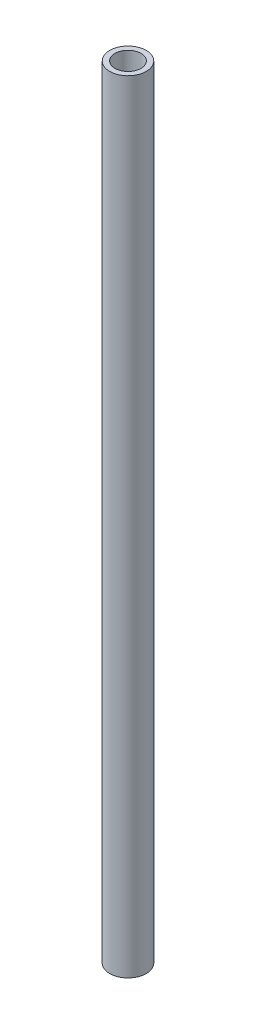
SolidWorks part; units mm, degrees
ref_plane "Płaszczyzna przednia" through (0, 0, 0) normal (0, 0, 1) x (1, 0, 0)
ref_plane "Płaszczyzna górna" through (0, 0, 0) normal (0, 1, 0) x (1, 0, 0)
ref_plane "Płaszczyzna prawa" through (0, 0, 0) normal (1, 0, 0) x (0, 0, -1)
sketch "Sketch1" plane through (0, 0, 0) normal (0, 1, 0) x (1, 0, 0)
  circle A0 centre (0, 0) radius 7
  circle A1 centre (0, 0) radius 4
  dimension "D1" = 3
  dimension "D2" = 14
extrude "Boss-Extrude1" add sketch "Sketch1" along normal blind 300
sketch "Sketch2" plane through (0, 300, 0) normal (0, 1, 0) x (1, 0, 0)
  circle A1 centre (0, 0) radius 5
  dimension "D1" = 10
extrude "Cut-Extrude1" cut sketch "Sketch2" against normal blind 31
extrude "Cut-Extrude2" cut sketch "Sketch2<2>" along normal blind 31 from surface starting at face at (0, 0, 7)
sketch "Sketch2<2>" plane through (0, 300, 0) normal (0, 1, 0) x (1, 0, 0) same geometry as "Sketch2"
equation "\"G\"= 3'grubość ścianki"
equation "\"L\"= 300'długość całkowita"
equation "\"G1\"= 31'głębokość gwintu"
